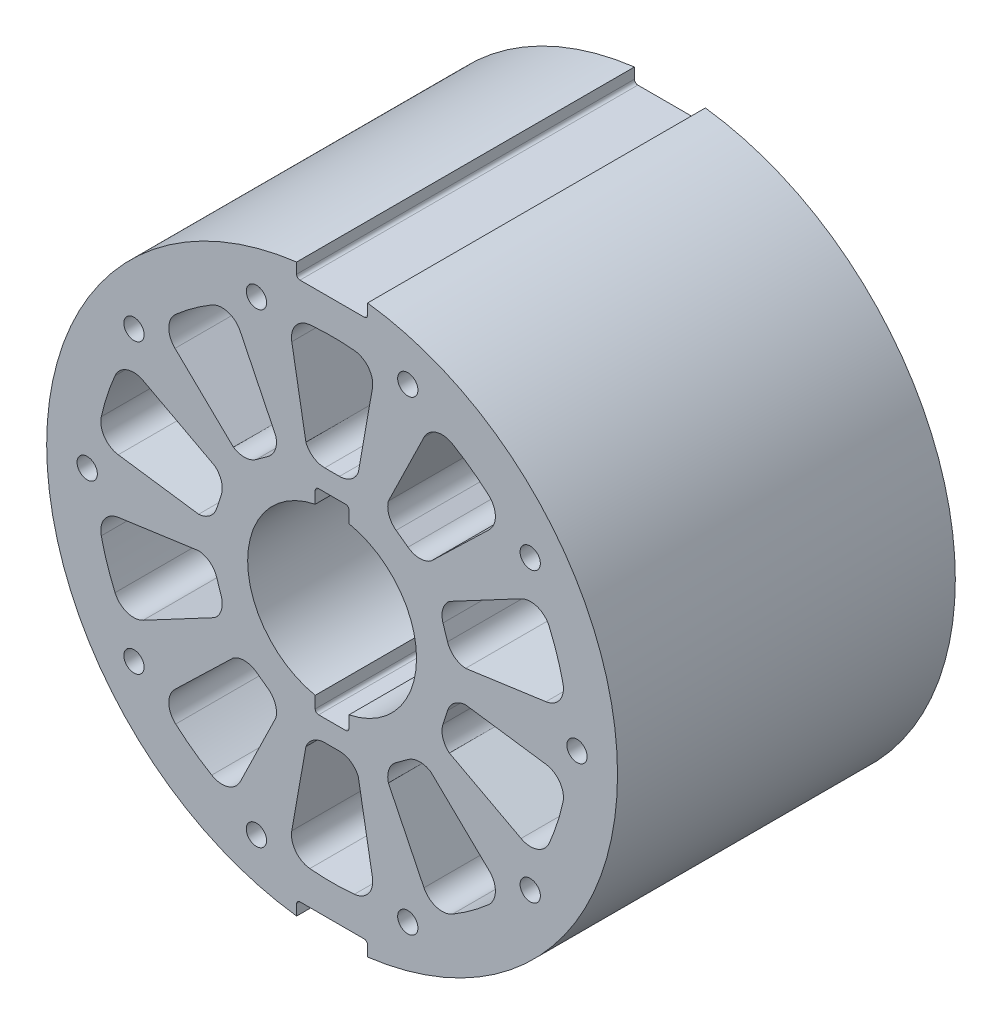
SolidWorks part; units mm, degrees
ref_plane "Ön Düzlem" through (0, 0, 0) normal (0, 0, 1) x (1, 0, 0)
ref_plane "Üst Düzlem" through (0, 0, 0) normal (0, 1, 0) x (1, 0, 0)
ref_plane "Sağ Düzlem" through (0, 0, 0) normal (1, 0, 0) x (0, 0, -1)
sketch "Model" plane through (0, 0, 0) normal (0, 0, 1) x (1, 0, 0)
  line L0 (-9.5, 79.7049) -> (9.5, 79.7049)
  line L1 (60.5945, 121.4987) -> (60.8885, 121.3363)
  line L2 (60.8885, 121.3363) -> (61.139, 121.1124)
  line L3 (61.139, 121.1124) -> (61.3334, 120.8385)
  line L4 (61.3334, 120.8385) -> (61.4619, 120.5282)
  line L5 (61.4619, 120.5282) -> (61.5182, 120.197)
  line L6 (61.5182, 120.197) -> (61.4993, 119.8617)
  line L7 (61.4993, 119.8617) -> (61.4063, 119.5389)
  line L8 (61.4063, 119.5389) -> (45.7726, 92.4605)
  line L9 (45.7726, 92.4605) -> (42.0525, 92.3778)
  line L10 (42.0525, 92.3778) -> (41.4785, 90.992)
  line L11 (58.0621, 81.4174) -> (58.9753, 82.6074)
  line L12 (58.9753, 82.6074) -> (57.1868, 85.8705)
  line L13 (57.1868, 85.8705) -> (72.8206, 112.9489)
  line L14 (72.8206, 112.9489) -> (73.0536, 113.1908)
  line L15 (73.0536, 113.1908) -> (73.3346, 113.3748)
  line L16 (73.3346, 113.3748) -> (73.6495, 113.4917)
  line L17 (73.6495, 113.4917) -> (73.9825, 113.5355)
  line L18 (73.9825, 113.5355) -> (74.317, 113.5041)
  line L19 (74.317, 113.5041) -> (74.636, 113.3991)
  line L20 (74.636, 113.3991) -> (74.9237, 113.2258)
  line L21 (74.9237, 113.2258) -> (89.976, 101.6758)
  line L22 (89.976, 101.6758) -> (90.2179, 101.4427)
  line L23 (90.2179, 101.4427) -> (90.4019, 101.1617)
  line L24 (90.4019, 101.1617) -> (90.5188, 100.8468)
  line L25 (90.5188, 100.8468) -> (90.5626, 100.5138)
  line L26 (90.5626, 100.5138) -> (90.5313, 100.1793)
  line L27 (90.5313, 100.1793) -> (90.4263, 99.8603)
  line L28 (90.4263, 99.8603) -> (90.2529, 99.5726)
  line L29 (90.2529, 99.5726) -> (68.1435, 77.4631)
  line L30 (68.1435, 77.4631) -> (64.5287, 78.3461)
  line L31 (64.5287, 78.3461) -> (63.6156, 77.1561)
  line L32 (77.1561, 63.6156) -> (78.3461, 64.5287)
  line L33 (78.3461, 64.5287) -> (77.4631, 68.1435)
  line L34 (77.4631, 68.1435) -> (99.5726, 90.2529)
  line L35 (99.5726, 90.2529) -> (99.8603, 90.4263)
  line L36 (99.8603, 90.4263) -> (100.1793, 90.5313)
  line L37 (100.1793, 90.5313) -> (100.5138, 90.5626)
  line L38 (100.5138, 90.5626) -> (100.8468, 90.5188)
  line L39 (100.8468, 90.5188) -> (101.1617, 90.4019)
  line L40 (101.1617, 90.4019) -> (101.4427, 90.2179)
  line L41 (101.4427, 90.2179) -> (101.6758, 89.976)
  line L42 (101.6758, 89.976) -> (113.2258, 74.9237)
  line L43 (113.2258, 74.9237) -> (113.3991, 74.636)
  line L44 (113.3991, 74.636) -> (113.5041, 74.317)
  line L45 (113.5041, 74.317) -> (113.5355, 73.9825)
  line L46 (113.5355, 73.9825) -> (113.4917, 73.6495)
  line L47 (113.4917, 73.6495) -> (113.3748, 73.3346)
  line L48 (113.3748, 73.3346) -> (113.1908, 73.0536)
  line L49 (113.1908, 73.0536) -> (112.9489, 72.8206)
  line L50 (112.9489, 72.8206) -> (85.8705, 57.1868)
  line L51 (85.8705, 57.1868) -> (82.6074, 58.9753)
  line L52 (82.6074, 58.9753) -> (81.4174, 58.0621)
  line L53 (90.992, 41.4785) -> (92.3778, 42.0525)
  line L54 (92.3778, 42.0525) -> (92.4605, 45.7726)
  line L55 (92.4605, 45.7726) -> (119.5389, 61.4063)
  line L56 (119.5389, 61.4063) -> (119.8617, 61.4993)
  line L57 (119.8617, 61.4993) -> (120.197, 61.5182)
  line L58 (120.197, 61.5182) -> (120.5282, 61.4619)
  line L59 (120.5282, 61.4619) -> (120.8385, 61.3334)
  line L60 (120.8385, 61.3334) -> (121.1124, 61.139)
  line L61 (121.1124, 61.139) -> (121.3363, 60.8885)
  line L62 (121.3363, 60.8885) -> (121.4987, 60.5945)
  line L63 (121.4987, 60.5945) -> (128.7594, 43.0658)
  line L64 (128.7594, 43.0658) -> (128.8524, 42.743)
  line L65 (128.8524, 42.743) -> (128.8712, 42.4076)
  line L66 (128.8712, 42.4076) -> (128.815, 42.0765)
  line L67 (128.815, 42.0765) -> (128.6864, 41.7662)
  line L68 (128.6864, 41.7662) -> (128.492, 41.4922)
  line L69 (128.492, 41.4922) -> (128.2416, 41.2684)
  line L70 (128.2416, 41.2684) -> (127.9476, 41.1059)
  line L71 (127.9476, 41.1059) -> (97.7455, 33.0133)
  line L72 (97.7455, 33.0133) -> (95.0566, 35.5853)
  line L73 (95.0566, 35.5853) -> (93.6707, 35.0113)
  line L74 (98.6269, 16.5147) -> (100.1141, 16.7105)
  line L75 (100.1141, 16.7105) -> (101.1568, 20.2824)
  line L76 (101.1568, 20.2824) -> (131.3588, 28.375)
  line L77 (131.3588, 28.375) -> (131.6947, 28.3813)
  line L78 (131.6947, 28.3813) -> (132.0235, 28.3127)
  line L79 (132.0235, 28.3127) -> (132.3288, 28.1726)
  line L80 (132.3288, 28.1726) -> (132.5953, 27.9682)
  line L81 (132.5953, 27.9682) -> (132.8096, 27.7095)
  line L82 (132.8096, 27.7095) -> (132.9609, 27.4097)
  line L83 (132.9609, 27.4097) -> (133.0418, 27.0836)
  line L84 (133.0418, 27.0836) -> (135.5183, 8.273)
  line L85 (135.5183, 8.273) -> (135.5246, 7.9371)
  line L86 (135.5246, 7.9371) -> (135.4559, 7.6083)
  line L87 (135.4559, 7.6083) -> (135.3159, 7.303)
  line L88 (135.3159, 7.303) -> (135.1114, 7.0365)
  line L89 (135.1114, 7.0365) -> (134.8528, 6.8222)
  line L90 (134.8528, 6.8222) -> (134.5529, 6.6709)
  line L91 (134.5529, 6.6709) -> (134.2269, 6.59)
  line L92 (134.2269, 6.59) -> (102.9594, 6.59)
  line L93 (102.9594, 6.59) -> (101.0278, 9.7704)
  line L94 (101.0278, 9.7704) -> (99.5406, 9.5746)
  line L95 (99.5406, -9.5746) -> (101.0278, -9.7704)
  line L96 (101.0278, -9.7704) -> (102.9594, -6.59)
  line L97 (102.9594, -6.59) -> (134.2269, -6.59)
  line L98 (134.2269, -6.59) -> (134.5529, -6.6709)
  line L99 (134.5529, -6.6709) -> (134.8528, -6.8222)
  line L100 (134.8528, -6.8222) -> (135.1114, -7.0365)
  line L101 (135.1114, -7.0365) -> (135.3159, -7.303)
  line L102 (135.3159, -7.303) -> (135.4559, -7.6083)
  line L103 (135.4559, -7.6083) -> (135.5246, -7.9371)
  line L104 (135.5246, -7.9371) -> (135.5183, -8.273)
  line L105 (135.5183, -8.273) -> (133.0418, -27.0836)
  line L106 (133.0418, -27.0836) -> (132.9609, -27.4097)
  line L107 (132.9609, -27.4097) -> (132.8096, -27.7095)
  line L108 (132.8096, -27.7095) -> (132.5953, -27.9682)
  line L109 (132.5953, -27.9682) -> (132.3288, -28.1726)
  line L110 (132.3288, -28.1726) -> (132.0235, -28.3127)
  line L111 (132.0235, -28.3127) -> (131.6947, -28.3813)
  line L112 (131.6947, -28.3813) -> (131.3588, -28.375)
  line L113 (131.3588, -28.375) -> (101.1568, -20.2824)
  line L114 (101.1568, -20.2824) -> (100.1141, -16.7105)
  line L115 (100.1141, -16.7105) -> (98.6269, -16.5147)
  line L116 (93.6707, -35.0113) -> (95.0566, -35.5853)
  line L117 (95.0566, -35.5853) -> (97.7455, -33.0133)
  line L118 (97.7455, -33.0133) -> (127.9476, -41.1059)
  line L119 (127.9476, -41.1059) -> (128.2416, -41.2684)
  line L120 (128.2416, -41.2684) -> (128.492, -41.4922)
  line L121 (128.492, -41.4922) -> (128.6864, -41.7662)
  line L122 (128.6864, -41.7662) -> (128.815, -42.0765)
  line L123 (128.815, -42.0765) -> (128.8712, -42.4076)
  line L124 (128.8712, -42.4076) -> (128.8524, -42.743)
  line L125 (128.8524, -42.743) -> (128.7594, -43.0658)
  line L126 (128.7594, -43.0658) -> (121.4987, -60.5945)
  line L127 (121.4987, -60.5945) -> (121.3363, -60.8885)
  line L128 (121.3363, -60.8885) -> (121.1124, -61.139)
  line L129 (121.1124, -61.139) -> (120.8385, -61.3334)
  line L130 (120.8385, -61.3334) -> (120.5282, -61.4619)
  line L131 (120.5282, -61.4619) -> (120.197, -61.5182)
  line L132 (120.197, -61.5182) -> (119.8617, -61.4993)
  line L133 (119.8617, -61.4993) -> (119.5389, -61.4063)
  line L134 (119.5389, -61.4063) -> (92.4605, -45.7726)
  line L135 (92.4605, -45.7726) -> (92.3778, -42.0525)
  line L136 (92.3778, -42.0525) -> (90.992, -41.4785)
  line L137 (81.4174, -58.0621) -> (82.6074, -58.9753)
  line L138 (82.6074, -58.9753) -> (85.8705, -57.1868)
  line L139 (85.8705, -57.1868) -> (112.9489, -72.8206)
  line L140 (112.9489, -72.8206) -> (113.1908, -73.0536)
  line L141 (113.1908, -73.0536) -> (113.3748, -73.3346)
  line L142 (113.3748, -73.3346) -> (113.4917, -73.6495)
  line L143 (113.4917, -73.6495) -> (113.5355, -73.9825)
  line L144 (113.5355, -73.9825) -> (113.5041, -74.317)
  line L145 (113.5041, -74.317) -> (113.3991, -74.636)
  line L146 (113.3991, -74.636) -> (113.2258, -74.9237)
  line L147 (113.2258, -74.9237) -> (101.6758, -89.976)
  line L148 (101.6758, -89.976) -> (101.4427, -90.2179)
  line L149 (101.4427, -90.2179) -> (101.1617, -90.4019)
  line L150 (101.1617, -90.4019) -> (100.8468, -90.5188)
  line L151 (100.8468, -90.5188) -> (100.5138, -90.5626)
  line L152 (100.5138, -90.5626) -> (100.1793, -90.5313)
  line L153 (100.1793, -90.5313) -> (99.8603, -90.4263)
  line L154 (99.8603, -90.4263) -> (99.5726, -90.2529)
  line L155 (99.5726, -90.2529) -> (77.4631, -68.1435)
  line L156 (77.4631, -68.1435) -> (78.3461, -64.5287)
  line L157 (78.3461, -64.5287) -> (77.1561, -63.6156)
  line L158 (63.6156, -77.1561) -> (64.5287, -78.3461)
  line L159 (64.5287, -78.3461) -> (68.1435, -77.4631)
  line L160 (68.1435, -77.4631) -> (90.2529, -99.5726)
  line L161 (90.2529, -99.5726) -> (90.4263, -99.8603)
  line L162 (90.4263, -99.8603) -> (90.5313, -100.1793)
  line L163 (90.5313, -100.1793) -> (90.5626, -100.5138)
  line L164 (90.5626, -100.5138) -> (90.5188, -100.8468)
  line L165 (90.5188, -100.8468) -> (90.4019, -101.1617)
  line L166 (90.4019, -101.1617) -> (90.2179, -101.4427)
  line L167 (90.2179, -101.4427) -> (89.976, -101.6758)
  line L168 (89.976, -101.6758) -> (74.9237, -113.2258)
  line L169 (74.9237, -113.2258) -> (74.636, -113.3991)
  line L170 (74.636, -113.3991) -> (74.317, -113.5041)
  line L171 (74.317, -113.5041) -> (73.9825, -113.5355)
  line L172 (73.9825, -113.5355) -> (73.6495, -113.4917)
  line L173 (73.6495, -113.4917) -> (73.3346, -113.3748)
  line L174 (73.3346, -113.3748) -> (73.0536, -113.1908)
  line L175 (73.0536, -113.1908) -> (72.8206, -112.9489)
  line L176 (72.8206, -112.9489) -> (57.1868, -85.8705)
  line L177 (57.1868, -85.8705) -> (58.9753, -82.6074)
  line L178 (58.9753, -82.6074) -> (58.0621, -81.4174)
  line L179 (41.4785, -90.992) -> (42.0525, -92.3778)
  line L180 (42.0525, -92.3778) -> (45.7726, -92.4605)
  line L181 (45.7726, -92.4605) -> (61.4063, -119.5389)
  line L182 (61.4063, -119.5389) -> (61.4993, -119.8617)
  line L183 (61.4993, -119.8617) -> (61.5182, -120.197)
  line L184 (61.5182, -120.197) -> (61.4619, -120.5282)
  line L185 (61.4619, -120.5282) -> (61.3334, -120.8385)
  line L186 (61.3334, -120.8385) -> (61.139, -121.1124)
  line L187 (61.139, -121.1124) -> (60.8885, -121.3363)
  line L188 (60.8885, -121.3363) -> (60.5945, -121.4987)
  line L189 (60.5945, -121.4987) -> (43.0658, -128.7594)
  line L190 (43.0658, -128.7594) -> (42.743, -128.8524)
  line L191 (42.743, -128.8524) -> (42.4076, -128.8712)
  line L192 (42.4076, -128.8712) -> (42.0765, -128.815)
  line L193 (42.0765, -128.815) -> (41.7662, -128.6864)
  line L194 (41.7662, -128.6864) -> (41.4922, -128.492)
  line L195 (41.4922, -128.492) -> (41.2684, -128.2416)
  line L196 (41.2684, -128.2416) -> (41.1059, -127.9476)
  line L197 (41.1059, -127.9476) -> (33.0133, -97.7455)
  line L198 (33.0133, -97.7455) -> (35.5853, -95.0566)
  line L199 (35.5853, -95.0566) -> (35.0113, -93.6707)
  line L200 (16.5147, -98.6269) -> (16.7105, -100.1141)
  line L201 (16.7105, -100.1141) -> (20.2824, -101.1568)
  line L202 (20.2824, -101.1568) -> (28.375, -131.3588)
  line L203 (28.375, -131.3588) -> (28.3813, -131.6947)
  line L204 (28.3813, -131.6947) -> (28.3127, -132.0235)
  line L205 (28.3127, -132.0235) -> (28.1726, -132.3288)
  line L206 (28.1726, -132.3288) -> (27.9682, -132.5953)
  line L207 (27.9682, -132.5953) -> (27.7095, -132.8096)
  line L208 (27.7095, -132.8096) -> (27.4097, -132.9609)
  line L209 (27.4097, -132.9609) -> (27.0836, -133.0418)
  line L210 (27.0836, -133.0418) -> (8.273, -135.5183)
  line L211 (8.273, -135.5183) -> (7.9371, -135.5246)
  line L212 (7.9371, -135.5246) -> (7.6083, -135.4559)
  line L213 (7.6083, -135.4559) -> (7.303, -135.3159)
  line L214 (7.303, -135.3159) -> (7.0365, -135.1114)
  line L215 (7.0365, -135.1114) -> (6.8222, -134.8528)
  line L216 (6.8222, -134.8528) -> (6.6709, -134.5529)
  line L217 (6.6709, -134.5529) -> (6.59, -134.2269)
  line L218 (6.59, -134.2269) -> (6.59, -102.9594)
  line L219 (6.59, -102.9594) -> (9.7704, -101.0278)
  line L220 (9.7704, -101.0278) -> (9.5746, -99.5406)
  line L221 (-9.5746, -99.5406) -> (-9.7704, -101.0278)
  line L222 (-9.7704, -101.0278) -> (-6.59, -102.9594)
  line L223 (-6.59, -102.9594) -> (-6.59, -134.2269)
  line L224 (-6.59, -134.2269) -> (-6.6709, -134.5529)
  line L225 (-6.6709, -134.5529) -> (-6.8222, -134.8528)
  line L226 (-6.8222, -134.8528) -> (-7.0365, -135.1114)
  line L227 (-7.0365, -135.1114) -> (-7.303, -135.3159)
  line L228 (-7.303, -135.3159) -> (-7.6083, -135.4559)
  line L229 (-7.6083, -135.4559) -> (-7.9371, -135.5246)
  line L230 (-7.9371, -135.5246) -> (-8.273, -135.5183)
  line L231 (-8.273, -135.5183) -> (-27.0836, -133.0418)
  line L232 (-27.0836, -133.0418) -> (-27.4097, -132.9609)
  line L233 (-27.4097, -132.9609) -> (-27.7095, -132.8096)
  line L234 (-27.7095, -132.8096) -> (-27.9682, -132.5953)
  line L235 (-27.9682, -132.5953) -> (-28.1726, -132.3288)
  line L236 (-28.1726, -132.3288) -> (-28.3127, -132.0235)
  line L237 (-28.3127, -132.0235) -> (-28.3813, -131.6947)
  line L238 (-28.3813, -131.6947) -> (-28.375, -131.3588)
  line L239 (-28.375, -131.3588) -> (-20.2824, -101.1568)
  line L240 (-20.2824, -101.1568) -> (-16.7105, -100.1141)
  line L241 (-16.7105, -100.1141) -> (-16.5147, -98.6269)
  line L242 (-35.0113, -93.6707) -> (-35.5853, -95.0566)
  line L243 (-35.5853, -95.0566) -> (-33.0133, -97.7455)
  line L244 (-33.0133, -97.7455) -> (-41.1059, -127.9476)
  line L245 (-41.1059, -127.9476) -> (-41.2684, -128.2416)
  line L246 (-41.2684, -128.2416) -> (-41.4922, -128.492)
  line L247 (-41.4922, -128.492) -> (-41.7662, -128.6864)
  line L248 (-41.7662, -128.6864) -> (-42.0765, -128.815)
  line L249 (-42.0765, -128.815) -> (-42.4076, -128.8712)
  line L250 (-42.4076, -128.8712) -> (-42.743, -128.8524)
  line L251 (-42.743, -128.8524) -> (-43.0658, -128.7594)
  line L252 (-43.0658, -128.7594) -> (-60.5945, -121.4987)
  line L253 (-60.5945, -121.4987) -> (-60.8885, -121.3363)
  line L254 (-60.8885, -121.3363) -> (-61.139, -121.1124)
  line L255 (-61.139, -121.1124) -> (-61.3334, -120.8385)
  line L256 (-61.3334, -120.8385) -> (-61.4619, -120.5282)
  line L257 (-61.4619, -120.5282) -> (-61.5182, -120.197)
  line L258 (-61.5182, -120.197) -> (-61.4993, -119.8617)
  line L259 (-61.4993, -119.8617) -> (-61.4063, -119.5389)
  line L260 (-61.4063, -119.5389) -> (-45.7726, -92.4605)
  line L261 (-45.7726, -92.4605) -> (-42.0525, -92.3778)
  line L262 (-42.0525, -92.3778) -> (-41.4785, -90.992)
  line L263 (-58.0621, -81.4174) -> (-58.9753, -82.6074)
  line L264 (-58.9753, -82.6074) -> (-57.1868, -85.8705)
  line L265 (-57.1868, -85.8705) -> (-72.8206, -112.9489)
  line L266 (-72.8206, -112.9489) -> (-73.0536, -113.1908)
  line L267 (-73.0536, -113.1908) -> (-73.3346, -113.3748)
  line L268 (-73.3346, -113.3748) -> (-73.6495, -113.4917)
  line L269 (-73.6495, -113.4917) -> (-73.9825, -113.5355)
  line L270 (-73.9825, -113.5355) -> (-74.317, -113.5041)
  line L271 (-74.317, -113.5041) -> (-74.636, -113.3991)
  line L272 (-74.636, -113.3991) -> (-74.9237, -113.2258)
  line L273 (-74.9237, -113.2258) -> (-89.976, -101.6758)
  line L274 (-89.976, -101.6758) -> (-90.2179, -101.4427)
  line L275 (-90.2179, -101.4427) -> (-90.4019, -101.1617)
  line L276 (-90.4019, -101.1617) -> (-90.5188, -100.8468)
  line L277 (-90.5188, -100.8468) -> (-90.5626, -100.5138)
  line L278 (-90.5626, -100.5138) -> (-90.5313, -100.1793)
  line L279 (-90.5313, -100.1793) -> (-90.4263, -99.8603)
  line L280 (-90.4263, -99.8603) -> (-90.2529, -99.5726)
  line L281 (-90.2529, -99.5726) -> (-68.1435, -77.4631)
  line L282 (-68.1435, -77.4631) -> (-64.5287, -78.3461)
  line L283 (-64.5287, -78.3461) -> (-63.6156, -77.1561)
  line L284 (-77.1561, -63.6156) -> (-78.3461, -64.5287)
  line L285 (-78.3461, -64.5287) -> (-77.4631, -68.1435)
  line L286 (-77.4631, -68.1435) -> (-99.5726, -90.2529)
  line L287 (-99.5726, -90.2529) -> (-99.8603, -90.4263)
  line L288 (-99.8603, -90.4263) -> (-100.1793, -90.5313)
  line L289 (-100.1793, -90.5313) -> (-100.5138, -90.5626)
  line L290 (-100.5138, -90.5626) -> (-100.8468, -90.5188)
  line L291 (-100.8468, -90.5188) -> (-101.1617, -90.4019)
  line L292 (-101.1617, -90.4019) -> (-101.4427, -90.2179)
  line L293 (-101.4427, -90.2179) -> (-101.6758, -89.976)
  line L294 (-101.6758, -89.976) -> (-113.2258, -74.9237)
  line L295 (-113.2258, -74.9237) -> (-113.3991, -74.636)
  line L296 (-113.3991, -74.636) -> (-113.5041, -74.317)
  line L297 (-113.5041, -74.317) -> (-113.5355, -73.9825)
  line L298 (-113.5355, -73.9825) -> (-113.4917, -73.6495)
  line L299 (-113.4917, -73.6495) -> (-113.3748, -73.3346)
  line L300 (-113.3748, -73.3346) -> (-113.1908, -73.0536)
  line L301 (-113.1908, -73.0536) -> (-112.9489, -72.8206)
  line L302 (-112.9489, -72.8206) -> (-85.8705, -57.1868)
  line L303 (-85.8705, -57.1868) -> (-82.6074, -58.9753)
  line L304 (-82.6074, -58.9753) -> (-81.4174, -58.0621)
  line L305 (-90.992, -41.4785) -> (-92.3778, -42.0525)
  line L306 (-92.3778, -42.0525) -> (-92.4605, -45.7726)
  line L307 (-92.4605, -45.7726) -> (-119.5389, -61.4063)
  line L308 (-119.5389, -61.4063) -> (-119.8617, -61.4993)
  line L309 (-119.8617, -61.4993) -> (-120.197, -61.5182)
  line L310 (-120.197, -61.5182) -> (-120.5282, -61.4619)
  line L311 (-120.5282, -61.4619) -> (-120.8385, -61.3334)
  line L312 (-120.8385, -61.3334) -> (-121.1124, -61.139)
  line L313 (-121.1124, -61.139) -> (-121.3363, -60.8885)
  line L314 (-121.3363, -60.8885) -> (-121.4987, -60.5945)
  line L315 (-121.4987, -60.5945) -> (-128.7594, -43.0658)
  line L316 (-128.7594, -43.0658) -> (-128.8524, -42.743)
  line L317 (-128.8524, -42.743) -> (-128.8712, -42.4076)
  line L318 (-128.8712, -42.4076) -> (-128.815, -42.0765)
  line L319 (-128.815, -42.0765) -> (-128.6864, -41.7662)
  line L320 (-128.6864, -41.7662) -> (-128.492, -41.4922)
  line L321 (-128.492, -41.4922) -> (-128.2416, -41.2684)
  line L322 (-128.2416, -41.2684) -> (-127.9476, -41.1059)
  line L323 (-127.9476, -41.1059) -> (-97.7455, -33.0133)
  line L324 (-97.7455, -33.0133) -> (-95.0566, -35.5853)
  line L325 (-95.0566, -35.5853) -> (-93.6707, -35.0113)
  line L326 (-98.6269, -16.5147) -> (-100.1141, -16.7105)
  line L327 (-100.1141, -16.7105) -> (-101.1568, -20.2824)
  line L328 (-101.1568, -20.2824) -> (-131.3588, -28.375)
  line L329 (-131.3588, -28.375) -> (-131.6947, -28.3813)
  line L330 (-131.6947, -28.3813) -> (-132.0235, -28.3127)
  line L331 (-132.0235, -28.3127) -> (-132.3288, -28.1726)
  line L332 (-132.3288, -28.1726) -> (-132.5953, -27.9682)
  line L333 (-132.5953, -27.9682) -> (-132.8096, -27.7095)
  line L334 (-132.8096, -27.7095) -> (-132.9609, -27.4097)
  line L335 (-132.9609, -27.4097) -> (-133.0418, -27.0836)
  line L336 (-133.0418, -27.0836) -> (-135.5183, -8.273)
  line L337 (-135.5183, -8.273) -> (-135.5246, -7.9371)
  line L338 (-135.5246, -7.9371) -> (-135.4559, -7.6083)
  line L339 (-135.4559, -7.6083) -> (-135.3159, -7.303)
  line L340 (-135.3159, -7.303) -> (-135.1114, -7.0365)
  line L341 (-135.1114, -7.0365) -> (-134.8528, -6.8222)
  line L342 (-134.8528, -6.8222) -> (-134.5529, -6.6709)
  line L343 (-134.5529, -6.6709) -> (-134.2269, -6.59)
  line L344 (-134.2269, -6.59) -> (-102.9594, -6.59)
  line L345 (-102.9594, -6.59) -> (-101.0278, -9.7704)
  line L346 (-101.0278, -9.7704) -> (-99.5406, -9.5746)
  line L347 (-99.5406, 9.5746) -> (-101.0278, 9.7704)
  line L348 (-101.0278, 9.7704) -> (-102.9594, 6.59)
  line L349 (-102.9594, 6.59) -> (-134.2269, 6.59)
  line L350 (-134.2269, 6.59) -> (-134.5529, 6.6709)
  line L351 (-134.5529, 6.6709) -> (-134.8528, 6.8222)
  line L352 (-134.8528, 6.8222) -> (-135.1114, 7.0365)
  line L353 (-135.1114, 7.0365) -> (-135.3159, 7.303)
  line L354 (-135.3159, 7.303) -> (-135.4559, 7.6083)
  line L355 (-135.4559, 7.6083) -> (-135.5246, 7.9371)
  line L356 (-135.5246, 7.9371) -> (-135.5183, 8.273)
  line L357 (-135.5183, 8.273) -> (-133.0418, 27.0836)
  line L358 (-133.0418, 27.0836) -> (-132.9609, 27.4097)
  line L359 (-132.9609, 27.4097) -> (-132.8096, 27.7095)
  line L360 (-132.8096, 27.7095) -> (-132.5953, 27.9682)
  line L361 (-132.5953, 27.9682) -> (-132.3288, 28.1726)
  line L362 (-132.3288, 28.1726) -> (-132.0235, 28.3127)
  line L363 (-132.0235, 28.3127) -> (-131.6947, 28.3813)
  line L364 (-131.6947, 28.3813) -> (-131.3588, 28.375)
  line L365 (-131.3588, 28.375) -> (-101.1568, 20.2824)
  line L366 (-101.1568, 20.2824) -> (-100.1141, 16.7105)
  line L367 (-100.1141, 16.7105) -> (-98.6269, 16.5147)
  line L368 (-93.6707, 35.0113) -> (-95.0566, 35.5853)
  line L369 (-95.0566, 35.5853) -> (-97.7455, 33.0133)
  line L370 (-97.7455, 33.0133) -> (-127.9476, 41.1059)
  line L371 (-127.9476, 41.1059) -> (-128.2416, 41.2684)
  line L372 (-128.2416, 41.2684) -> (-128.492, 41.4922)
  line L373 (-128.492, 41.4922) -> (-128.6864, 41.7662)
  line L374 (-128.6864, 41.7662) -> (-128.815, 42.0765)
  line L375 (-128.815, 42.0765) -> (-128.8712, 42.4076)
  line L376 (-128.8712, 42.4076) -> (-128.8524, 42.743)
  line L377 (-128.8524, 42.743) -> (-128.7594, 43.0658)
  line L378 (-128.7594, 43.0658) -> (-121.4987, 60.5945)
  line L379 (-121.4987, 60.5945) -> (-121.3363, 60.8885)
  line L380 (-121.3363, 60.8885) -> (-121.1124, 61.139)
  line L381 (-121.1124, 61.139) -> (-120.8385, 61.3334)
  line L382 (-120.8385, 61.3334) -> (-120.5282, 61.4619)
  line L383 (-120.5282, 61.4619) -> (-120.197, 61.5182)
  line L384 (-120.197, 61.5182) -> (-119.8617, 61.4993)
  line L385 (-119.8617, 61.4993) -> (-119.5389, 61.4063)
  line L386 (-119.5389, 61.4063) -> (-92.4605, 45.7726)
  line L387 (-92.4605, 45.7726) -> (-92.3778, 42.0525)
  line L388 (-92.3778, 42.0525) -> (-90.992, 41.4785)
  line L389 (-81.4174, 58.0621) -> (-82.6074, 58.9753)
  line L390 (-82.6074, 58.9753) -> (-85.8705, 57.1868)
  line L391 (-85.8705, 57.1868) -> (-112.9489, 72.8206)
  line L392 (-112.9489, 72.8206) -> (-113.1908, 73.0536)
  line L393 (-113.1908, 73.0536) -> (-113.3748, 73.3346)
  line L394 (-113.3748, 73.3346) -> (-113.4917, 73.6495)
  line L395 (-113.4917, 73.6495) -> (-113.5355, 73.9825)
  line L396 (-113.5355, 73.9825) -> (-113.5041, 74.317)
  line L397 (-113.5041, 74.317) -> (-113.3991, 74.636)
  line L398 (-113.3991, 74.636) -> (-113.2258, 74.9237)
  line L399 (-113.2258, 74.9237) -> (-101.6758, 89.976)
  line L400 (-101.6758, 89.976) -> (-101.4427, 90.2179)
  line L401 (-101.4427, 90.2179) -> (-101.1617, 90.4019)
  line L402 (-101.1617, 90.4019) -> (-100.8468, 90.5188)
  line L403 (-100.8468, 90.5188) -> (-100.5138, 90.5626)
  line L404 (-100.5138, 90.5626) -> (-100.1793, 90.5313)
  line L405 (-100.1793, 90.5313) -> (-99.8603, 90.4263)
  line L406 (-99.8603, 90.4263) -> (-99.5726, 90.2529)
  line L407 (-99.5726, 90.2529) -> (-77.4631, 68.1435)
  line L408 (-77.4631, 68.1435) -> (-78.3461, 64.5287)
  line L409 (-78.3461, 64.5287) -> (-77.1561, 63.6156)
  line L410 (-63.6156, 77.1561) -> (-64.5287, 78.3461)
  line L411 (-64.5287, 78.3461) -> (-68.1435, 77.4631)
  line L412 (-68.1435, 77.4631) -> (-90.2529, 99.5726)
  line L413 (-90.2529, 99.5726) -> (-90.4263, 99.8603)
  line L414 (-90.4263, 99.8603) -> (-90.5313, 100.1793)
  line L415 (-90.5313, 100.1793) -> (-90.5626, 100.5138)
  line L416 (-90.5626, 100.5138) -> (-90.5188, 100.8468)
  line L417 (-90.5188, 100.8468) -> (-90.4019, 101.1617)
  line L418 (-90.4019, 101.1617) -> (-90.2179, 101.4427)
  line L419 (-90.2179, 101.4427) -> (-89.976, 101.6758)
  line L420 (-89.976, 101.6758) -> (-74.9237, 113.2258)
  line L421 (-74.9237, 113.2258) -> (-74.636, 113.3991)
  line L422 (-74.636, 113.3991) -> (-74.317, 113.5041)
  line L423 (-74.317, 113.5041) -> (-73.9825, 113.5355)
  line L424 (-73.9825, 113.5355) -> (-73.6495, 113.4917)
  line L425 (-73.6495, 113.4917) -> (-73.3346, 113.3748)
  line L426 (-73.3346, 113.3748) -> (-73.0536, 113.1908)
  line L427 (-73.0536, 113.1908) -> (-72.8206, 112.9489)
  line L428 (-72.8206, 112.9489) -> (-57.1868, 85.8705)
  line L429 (-57.1868, 85.8705) -> (-58.9753, 82.6074)
  line L430 (-58.9753, 82.6074) -> (-58.0621, 81.4174)
  line L431 (-41.4785, 90.992) -> (-42.0525, 92.3778)
  line L432 (-42.0525, 92.3778) -> (-45.7726, 92.4605)
  line L433 (-45.7726, 92.4605) -> (-61.4063, 119.5389)
  line L434 (-61.4063, 119.5389) -> (-61.4993, 119.8617)
  line L435 (-61.4993, 119.8617) -> (-61.5182, 120.197)
  line L436 (-61.5182, 120.197) -> (-61.4619, 120.5282)
  line L437 (-61.4619, 120.5282) -> (-61.3334, 120.8385)
  line L438 (-61.3334, 120.8385) -> (-61.139, 121.1124)
  line L439 (-61.139, 121.1124) -> (-60.8885, 121.3363)
  line L440 (-60.8885, 121.3363) -> (-60.5945, 121.4987)
  line L441 (-60.5945, 121.4987) -> (-43.0658, 128.7594)
  line L442 (-43.0658, 128.7594) -> (-42.743, 128.8524)
  line L443 (-42.743, 128.8524) -> (-42.4076, 128.8712)
  line L444 (-42.4076, 128.8712) -> (-42.0765, 128.815)
  line L445 (-42.0765, 128.815) -> (-41.7662, 128.6864)
  line L446 (-41.7662, 128.6864) -> (-41.4922, 128.492)
  line L447 (-41.4922, 128.492) -> (-41.2684, 128.2416)
  line L448 (-41.2684, 128.2416) -> (-41.1059, 127.9476)
  line L449 (-41.1059, 127.9476) -> (-33.0133, 97.7455)
  line L450 (-33.0133, 97.7455) -> (-35.5853, 95.0566)
  line L451 (-35.5853, 95.0566) -> (-35.0113, 93.6707)
  line L452 (-16.5147, 98.6269) -> (-16.7105, 100.1141)
  line L453 (-16.7105, 100.1141) -> (-20.2824, 101.1568)
  line L454 (-20.2824, 101.1568) -> (-28.375, 131.3588)
  line L455 (-28.375, 131.3588) -> (-28.3813, 131.6947)
  line L456 (-28.3813, 131.6947) -> (-28.3127, 132.0235)
  line L457 (-28.3127, 132.0235) -> (-28.1726, 132.3288)
  line L458 (-28.1726, 132.3288) -> (-27.9682, 132.5953)
  line L459 (-27.9682, 132.5953) -> (-27.7095, 132.8096)
  line L460 (-27.7095, 132.8096) -> (-27.4097, 132.9609)
  line L461 (-27.4097, 132.9609) -> (-27.0836, 133.0418)
  line L462 (-27.0836, 133.0418) -> (-8.273, 135.5183)
  line L463 (-8.273, 135.5183) -> (-7.9371, 135.5246)
  line L464 (-7.9371, 135.5246) -> (-7.6083, 135.4559)
  line L465 (-7.6083, 135.4559) -> (-7.303, 135.3159)
  line L466 (-7.303, 135.3159) -> (-7.0365, 135.1114)
  line L467 (-7.0365, 135.1114) -> (-6.8222, 134.8528)
  line L468 (-6.8222, 134.8528) -> (-6.6709, 134.5529)
  line L469 (-6.6709, 134.5529) -> (-6.59, 134.2269)
  line L470 (-6.59, 134.2269) -> (-6.59, 102.9594)
  line L471 (-6.59, 102.9594) -> (-9.7704, 101.0278)
  line L472 (-9.7704, 101.0278) -> (-9.5746, 99.5406)
  line L473 (9.5746, 99.5406) -> (9.7704, 101.0278)
  line L474 (9.7704, 101.0278) -> (6.59, 102.9594)
  line L475 (6.59, 102.9594) -> (6.59, 134.2269)
  line L476 (6.59, 134.2269) -> (6.6709, 134.5529)
  line L477 (6.6709, 134.5529) -> (6.8222, 134.8528)
  line L478 (6.8222, 134.8528) -> (7.0365, 135.1114)
  line L479 (7.0365, 135.1114) -> (7.303, 135.3159)
  line L480 (7.303, 135.3159) -> (7.6083, 135.4559)
  line L481 (7.6083, 135.4559) -> (7.9371, 135.5246)
  line L482 (7.9371, 135.5246) -> (8.273, 135.5183)
  line L483 (8.273, 135.5183) -> (27.0836, 133.0418)
  line L484 (27.0836, 133.0418) -> (27.4097, 132.9609)
  line L485 (27.4097, 132.9609) -> (27.7095, 132.8096)
  line L486 (27.7095, 132.8096) -> (27.9682, 132.5953)
  line L487 (27.9682, 132.5953) -> (28.1726, 132.3288)
  line L488 (28.1726, 132.3288) -> (28.3127, 132.0235)
  line L489 (28.3127, 132.0235) -> (28.3813, 131.6947)
  line L490 (28.3813, 131.6947) -> (28.375, 131.3588)
  line L491 (28.375, 131.3588) -> (20.2824, 101.1568)
  line L492 (20.2824, 101.1568) -> (16.7105, 100.1141)
  line L493 (16.7105, 100.1141) -> (16.5147, 98.6269)
  line L494 (35.0113, 93.6707) -> (35.5853, 95.0566)
  line L495 (35.5853, 95.0566) -> (33.0133, 97.7455)
  line L496 (33.0133, 97.7455) -> (41.1059, 127.9476)
  line L497 (41.1059, 127.9476) -> (41.2684, 128.2416)
  line L498 (41.2684, 128.2416) -> (41.4922, 128.492)
  line L499 (41.4922, 128.492) -> (41.7662, 128.6864)
  line L500 (41.7662, 128.6864) -> (42.0765, 128.815)
  line L501 (42.0765, 128.815) -> (42.4076, 128.8712)
  line L502 (42.4076, 128.8712) -> (42.743, 128.8524)
  line L503 (42.743, 128.8524) -> (43.0658, 128.7594)
  line L504 (43.0658, 128.7594) -> (60.5945, 121.4987)
  line L505 (-9.5, 80.2049) -> (9.5, 80.2049)
  line L506 (10.5, 80.7049) -> (10.5, 83.8451)
  line L507 (10.5, -80.7049) -> (10.5, -83.8451)
  line L508 (27.7776, -94.5021) -> (26.5086, -90.1848)
  line L509 (2.6574, -93.9624) -> (2.7847, -98.4606)
  line L510 (-27.7776, 94.5021) -> (-26.5086, 90.1848)
  line L511 (-2.6574, 93.9624) -> (-2.7847, 98.4606)
  line L512 (94.5021, 27.7776) -> (90.1848, 26.5086)
  line L513 (93.9624, 2.6574) -> (98.4606, 2.7847)
  line L514 (-94.5021, -27.7776) -> (-90.1848, -26.5086)
  line L515 (-93.9624, -2.6574) -> (-98.4606, -2.7847)
  line L516 (55.6209, -81.2931) -> (53.0798, -77.5792)
  line L517 (31.5634, -88.5424) -> (33.0744, -92.7811)
  line L518 (-55.6209, 81.2931) -> (-53.0798, 77.5792)
  line L519 (-31.5634, 88.5424) -> (-33.0744, 92.7811)
  line L520 (81.2931, 55.6209) -> (77.5792, 53.0798)
  line L521 (88.5424, 31.5634) -> (92.7811, 33.0744)
  line L522 (-81.2931, -55.6209) -> (-77.5792, -53.0798)
  line L523 (-88.5424, -31.5634) -> (-92.7811, -33.0744)
  line L524 (78.0195, -60.1265) -> (74.4552, -57.3796)
  line L525 (57.3796, -74.4552) -> (60.1265, -78.0195)
  line L526 (-78.0195, 60.1265) -> (-74.4552, 57.3796)
  line L527 (-57.3796, 74.4552) -> (-60.1265, 78.0195)
  line L528 (60.1265, 78.0195) -> (57.3796, 74.4552)
  line L529 (74.4552, 57.3796) -> (78.0195, 60.1265)
  line L530 (-60.1265, -78.0195) -> (-57.3796, -74.4552)
  line L531 (-74.4552, -57.3796) -> (-78.0195, -60.1265)
  line L532 (92.7811, -33.0744) -> (88.5424, -31.5634)
  line L533 (77.5792, -53.0798) -> (81.2931, -55.6209)
  line L534 (-92.7811, 33.0744) -> (-88.5424, 31.5634)
  line L535 (-77.5792, 53.0798) -> (-81.2931, 55.6209)
  line L536 (33.0744, 92.7811) -> (31.5634, 88.5424)
  line L537 (53.0798, 77.5792) -> (55.6209, 81.2931)
  line L538 (-33.0744, -92.7811) -> (-31.5634, -88.5424)
  line L539 (-53.0798, -77.5792) -> (-55.6209, -81.2931)
  line L540 (98.4606, -2.7847) -> (93.9624, -2.6574)
  line L541 (90.1848, -26.5086) -> (94.5021, -27.7776)
  line L542 (-98.4606, 2.7847) -> (-93.9624, 2.6574)
  line L543 (-90.1848, 26.5086) -> (-94.5021, 27.7776)
  line L544 (2.7847, 98.4606) -> (2.6574, 93.9624)
  line L545 (26.5086, 90.1848) -> (27.7776, 94.5021)
  line L546 (-2.7847, -98.4606) -> (-2.6574, -93.9624)
  line L547 (-26.5086, -90.1848) -> (-27.7776, -94.5021)
  line L548 (9.5, -79.7049) -> (-9.5, -79.7049)
  line L549 (10, 80.7049) -> (10, 84.4097)
  line L550 (-10.5, -80.7049) -> (-10.5, -83.8451)
  line L551 (-10, 80.7049) -> (-10, 84.4097)
  line L552 (9.5, -80.2049) -> (-9.5, -80.2049)
  line L553 (-10, -80.7049) -> (-10, -84.4097)
  line L554 (10, -80.7049) -> (10, -84.4097)
  line L555 (-10.5, 80.7049) -> (-10.5, 83.8451)
  line L556 (-7.7629, 39.0257) -> (-11.9363, 62.6943)
  line L557 (7.7629, 39.0257) -> (11.9363, 62.6943)
  line L558 (16.6584, 36.1354) -> (27.1941, 57.7368)
  line L559 (29.2191, 27.0095) -> (46.5075, 43.7048)
  line L560 (22.4686, 27.2158) -> (18.9406, 29.779)
  line L561 (34.7168, 19.4426) -> (55.9373, 30.7257)
  line L562 (39.5145, 4.6766) -> (63.3144, 8.0215)
  line L563 (34.1745, 8.8113) -> (32.8269, 12.9587)
  line L564 (39.5145, -4.6766) -> (63.3144, -8.0215)
  line L565 (34.7168, -19.4426) -> (55.9373, -30.7257)
  line L566 (32.8269, -12.9587) -> (34.1745, -8.8113)
  line L567 (29.2191, -27.0095) -> (46.5075, -43.7048)
  line L568 (16.6584, -36.1354) -> (27.1941, -57.7368)
  line L569 (18.9406, -29.779) -> (22.4686, -27.2158)
  line L570 (7.7629, -39.0257) -> (11.9363, -62.6943)
  line L571 (-7.7629, -39.0257) -> (-11.9363, -62.6943)
  line L572 (-2.1804, -35.2247) -> (2.1804, -35.2247)
  line L573 (-16.6584, -36.1354) -> (-27.1941, -57.7368)
  line L574 (-29.2191, -27.0095) -> (-46.5075, -43.7048)
  line L575 (-22.4686, -27.2158) -> (-18.9406, -29.779)
  line L576 (-5, -24.4949) -> (-5, -27.9898)
  line L577 (5, 24.4949) -> (5, 27.9898)
  line L578 (-34.7168, -19.4426) -> (-55.9373, -30.7257)
  line L579 (-39.5145, -4.6766) -> (-63.3144, -8.0215)
  line L580 (2.1804, 35.2247) -> (-2.1804, 35.2247)
  line L581 (-34.1745, -8.8113) -> (-32.8269, -12.9587)
  line L582 (-39.5145, 4.6766) -> (-63.3144, 8.0215)
  line L583 (-34.7168, 19.4426) -> (-55.9373, 30.7257)
  line L584 (-32.8269, 12.9587) -> (-34.1745, 8.8113)
  line L585 (-29.2191, 27.0095) -> (-46.5075, 43.7048)
  line L586 (-16.6584, 36.1354) -> (-27.1941, 57.7368)
  line L587 (-18.9406, 29.779) -> (-22.4686, 27.2158)
  line L588 (-5, 24.4949) -> (-5, 27.9898)
  line L589 (0, 28.9898) -> (-4, 28.9898)
  line L590 (5, -24.4949) -> (5, -27.9898)
  line L591 (0, -28.9898) -> (4, -28.9898)
  line L592 (0, 28.9898) -> (4, 28.9898)
  line L593 (0, -28.9898) -> (-4, -28.9898)
  arc A0 (145, 0) -> (64.7137, 129.758) centre (0, 0) ccw
  arc A1 (58.0621, 81.4174) -> (41.4785, 90.992) centre (0, 0) ccw
  arc A2 (77.1561, 63.6156) -> (63.6156, 77.1561) centre (0, 0) ccw
  arc A3 (90.992, 41.4785) -> (81.4174, 58.0621) centre (0, 0) ccw
  arc A4 (98.6269, 16.5147) -> (93.6707, 35.0113) centre (0, 0) ccw
  arc A5 (99.5406, -9.5746) -> (99.5406, 9.5746) centre (0, 0) ccw
  arc A6 (93.6707, -35.0113) -> (98.6269, -16.5147) centre (0, 0) ccw
  arc A7 (81.4174, -58.0621) -> (90.992, -41.4785) centre (0, 0) ccw
  arc A8 (63.6156, -77.1561) -> (77.1561, -63.6156) centre (0, 0) ccw
  arc A9 (41.4785, -90.992) -> (58.0621, -81.4174) centre (0, 0) ccw
  arc A10 (16.5147, -98.6269) -> (35.0113, -93.6707) centre (0, 0) ccw
  arc A11 (-9.5746, -99.5406) -> (9.5746, -99.5406) centre (0, 0) ccw
  arc A12 (-35.0113, -93.6707) -> (-16.5147, -98.6269) centre (0, 0) ccw
  arc A13 (-58.0621, -81.4174) -> (-41.4785, -90.992) centre (0, 0) ccw
  arc A14 (-77.1561, -63.6156) -> (-63.6156, -77.1561) centre (0, 0) ccw
  arc A15 (-90.992, -41.4785) -> (-81.4174, -58.0621) centre (0, 0) ccw
  arc A16 (-98.6269, -16.5147) -> (-93.6707, -35.0113) centre (0, 0) ccw
  arc A17 (-99.5406, 9.5746) -> (-99.5406, -9.5746) centre (0, 0) ccw
  arc A18 (-93.6707, 35.0113) -> (-98.6269, 16.5147) centre (0, 0) ccw
  arc A19 (-81.4174, 58.0621) -> (-90.992, 41.4785) centre (0, 0) ccw
  arc A20 (-63.6156, 77.1561) -> (-77.1561, 63.6156) centre (0, 0) ccw
  arc A21 (-41.4785, 90.992) -> (-58.0621, 81.4174) centre (0, 0) ccw
  arc A22 (-16.5147, 98.6269) -> (-35.0113, 93.6707) centre (0, 0) ccw
  arc A23 (9.5746, 99.5406) -> (-9.5746, 99.5406) centre (0, 0) ccw
  arc A24 (35.0113, 93.6707) -> (16.5147, 98.6269) centre (0, 0) ccw
  arc A25 (64.7137, 129.758) -> (145, 0) centre (0, 0) ccw
  arc A26 (94, 0) -> (-94, 0) centre (0, 0) ccw
  arc A27 (-10, 84.4097) -> (-10, -84.4097) centre (0, 0) ccw
  arc A28 (-94, 0) -> (94, 0) centre (0, 0) ccw
  arc A29 (2.7847, -98.4606) -> (27.7776, -94.5021) centre (0, 0) ccw
  arc A30 (2.6574, -93.9624) -> (26.5086, -90.1848) centre (0, 0) ccw
  arc A31 (-2.7847, 98.4606) -> (-27.7776, 94.5021) centre (0, 0) ccw
  arc A32 (-2.6574, 93.9624) -> (-26.5086, 90.1848) centre (0, 0) ccw
  arc A33 (98.4606, 2.7847) -> (94.5021, 27.7776) centre (0, 0) ccw
  arc A34 (93.9624, 2.6574) -> (90.1848, 26.5086) centre (0, 0) ccw
  arc A35 (-98.4606, -2.7847) -> (-94.5021, -27.7776) centre (0, 0) ccw
  arc A36 (-93.9624, -2.6574) -> (-90.1848, -26.5086) centre (0, 0) ccw
  arc A37 (33.0744, -92.7811) -> (55.6209, -81.2931) centre (0, 0) ccw
  arc A38 (31.5634, -88.5424) -> (53.0798, -77.5792) centre (0, 0) ccw
  arc A39 (-33.0744, 92.7811) -> (-55.6209, 81.2931) centre (0, 0) ccw
  arc A40 (-31.5634, 88.5424) -> (-53.0798, 77.5792) centre (0, 0) ccw
  arc A41 (92.7811, 33.0744) -> (81.2931, 55.6209) centre (0, 0) ccw
  arc A42 (88.5424, 31.5634) -> (77.5792, 53.0798) centre (0, 0) ccw
  arc A43 (-92.7811, -33.0744) -> (-81.2931, -55.6209) centre (0, 0) ccw
  arc A44 (-88.5424, -31.5634) -> (-77.5792, -53.0798) centre (0, 0) ccw
  arc A45 (60.1265, -78.0195) -> (78.0195, -60.1265) centre (0, 0) ccw
  arc A46 (57.3796, -74.4552) -> (74.4552, -57.3796) centre (0, 0) ccw
  arc A47 (-60.1265, 78.0195) -> (-78.0195, 60.1265) centre (0, 0) ccw
  arc A48 (-57.3796, 74.4552) -> (-74.4552, 57.3796) centre (0, 0) ccw
  arc A49 (78.0195, 60.1265) -> (60.1265, 78.0195) centre (0, 0) ccw
  arc A50 (74.4552, 57.3796) -> (57.3796, 74.4552) centre (0, 0) ccw
  arc A51 (-78.0195, -60.1265) -> (-60.1265, -78.0195) centre (0, 0) ccw
  arc A52 (-74.4552, -57.3796) -> (-57.3796, -74.4552) centre (0, 0) ccw
  arc A53 (81.2931, -55.6209) -> (92.7811, -33.0744) centre (0, 0) ccw
  arc A54 (77.5792, -53.0798) -> (88.5424, -31.5634) centre (0, 0) ccw
  arc A55 (-81.2931, 55.6209) -> (-92.7811, 33.0744) centre (0, 0) ccw
  arc A56 (-77.5792, 53.0798) -> (-88.5424, 31.5634) centre (0, 0) ccw
  arc A57 (55.6209, 81.2931) -> (33.0744, 92.7811) centre (0, 0) ccw
  arc A58 (53.0798, 77.5792) -> (31.5634, 88.5424) centre (0, 0) ccw
  arc A59 (-55.6209, -81.2931) -> (-33.0744, -92.7811) centre (0, 0) ccw
  arc A60 (-53.0798, -77.5792) -> (-31.5634, -88.5424) centre (0, 0) ccw
  arc A61 (94.5021, -27.7776) -> (98.4606, -2.7847) centre (0, 0) ccw
  arc A62 (90.1848, -26.5086) -> (93.9624, -2.6574) centre (0, 0) ccw
  arc A63 (-94.5021, 27.7776) -> (-98.4606, 2.7847) centre (0, 0) ccw
  arc A64 (-90.1848, 26.5086) -> (-93.9624, 2.6574) centre (0, 0) ccw
  arc A65 (27.7776, 94.5021) -> (2.7847, 98.4606) centre (0, 0) ccw
  arc A66 (26.5086, 90.1848) -> (2.6574, 93.9624) centre (0, 0) ccw
  arc A67 (-27.7776, -94.5021) -> (-2.7847, -98.4606) centre (0, 0) ccw
  arc A68 (-26.5086, -90.1848) -> (-2.6574, -93.9624) centre (0, 0) ccw
  arc A69 (9.5, 80.2049) -> (10, 80.7049) centre (9.5, 80.7049) ccw
  arc A70 (-10, 80.7049) -> (-9.5, 80.2049) centre (-9.5, 80.7049) ccw
  arc A71 (-9.5, -80.2049) -> (-10, -80.7049) centre (-9.5, -80.7049) ccw
  arc A72 (10, -80.7049) -> (9.5, -80.2049) centre (9.5, -80.7049) ccw
  arc A73 (10, -84.4097) -> (10, 84.4097) centre (0, 0) ccw
  arc A74 (9.5, 79.7049) -> (10.5, 80.7049) centre (9.5, 80.7049) ccw
  arc A75 (10.5, -83.8451) -> (10.5, 83.8451) centre (0, 0) ccw
  arc A76 (10.5, -80.7049) -> (9.5, -79.7049) centre (9.5, -80.7049) ccw
  arc A77 (-9.5, -79.7049) -> (-10.5, -80.7049) centre (-9.5, -80.7049) ccw
  arc A78 (-10.5, 83.8451) -> (-10.5, -83.8451) centre (0, 0) ccw
  arc A79 (-10.5, 80.7049) -> (-9.5, 79.7049) centre (-9.5, 80.7049) ccw
  arc A80 (6.5924, 69.7096) -> (-6.5924, 69.7096) centre (0, 0) ccw
  arc A81 (-5, 24.4949) -> (-5, -24.4949) centre (0, 0) ccw
  arc A82 (2.1804, 35.2247) -> (7.7629, 39.0257) centre (2.1804, 41.2247) ccw
  arc A83 (46.3076, 52.5213) -> (35.6409, 60.2711) centre (0, 0) ccw
  arc A84 (22.4686, 27.2158) -> (29.2191, 27.0095) centre (25.9953, 32.0699) ccw
  arc A85 (46.3076, 52.5213) -> (46.5075, 43.7048) centre (42.3396, 48.0208) cw
  arc A86 (27.1941, 57.7368) -> (35.6409, 60.2711) centre (32.5869, 55.1066) cw
  arc A87 (18.9406, 29.779) -> (16.6584, 36.1354) centre (22.4673, 34.6331) cw
  arc A88 (68.3349, 15.2717) -> (64.2606, 27.8112) centre (0, 0) ccw
  arc A89 (34.1745, 8.8113) -> (39.5145, 4.6766) centre (39.8808, 10.6654) ccw
  arc A90 (68.3349, 15.2717) -> (63.3144, 8.0215) centre (62.4794, 13.9631) cw
  arc A91 (55.9373, 30.7257) -> (64.2606, 27.8112) centre (58.7542, 25.4281) cw
  arc A92 (32.8269, 12.9587) -> (34.7168, 19.4426) centre (38.5332, 14.8128) cw
  arc A93 (64.2606, -27.8112) -> (68.3349, -15.2717) centre (0, 0) ccw
  arc A94 (32.8269, -12.9587) -> (34.7168, -19.4426) centre (38.5332, -14.8128) ccw
  arc A95 (64.2606, -27.8112) -> (55.9373, -30.7257) centre (58.7542, -25.4281) cw
  arc A96 (63.3144, -8.0215) -> (68.3349, -15.2717) centre (62.4794, -13.9631) cw
  arc A97 (34.1745, -8.8113) -> (39.5145, -4.6766) centre (39.8808, -10.6654) cw
  arc A98 (6.5924, 69.7096) -> (11.9363, 62.6943) centre (6.0275, 63.7362) cw
  arc A99 (35.6409, -60.2711) -> (46.3076, -52.5213) centre (0, 0) ccw
  arc A100 (18.9406, -29.779) -> (16.6584, -36.1354) centre (22.4673, -34.6331) ccw
  arc A101 (-11.9363, 62.6943) -> (-6.5924, 69.7096) centre (-6.0275, 63.7362) cw
  arc A102 (35.6409, -60.2711) -> (27.1941, -57.7368) centre (32.5869, -55.1066) cw
  arc A103 (46.5075, -43.7048) -> (46.3076, -52.5213) centre (42.3396, -48.0208) cw
  arc A104 (22.4686, -27.2158) -> (29.2191, -27.0095) centre (25.9953, -32.0699) cw
  arc A105 (-6.5924, -69.7096) -> (6.5924, -69.7096) centre (0, 0) ccw
  arc A106 (-2.1804, -35.2247) -> (-7.7629, -39.0257) centre (-2.1804, -41.2247) ccw
  arc A107 (-6.5924, -69.7096) -> (-11.9363, -62.6943) centre (-6.0275, -63.7362) cw
  arc A108 (11.9363, -62.6943) -> (6.5924, -69.7096) centre (6.0275, -63.7362) cw
  arc A109 (2.1804, -35.2247) -> (7.7629, -39.0257) centre (2.1804, -41.2247) cw
  arc A110 (-46.3076, -52.5213) -> (-35.6409, -60.2711) centre (0, 0) ccw
  arc A111 (-22.4686, -27.2158) -> (-29.2191, -27.0095) centre (-25.9953, -32.0699) ccw
  arc A112 (-46.3076, -52.5213) -> (-46.5075, -43.7048) centre (-42.3396, -48.0208) cw
  arc A113 (-27.1941, -57.7368) -> (-35.6409, -60.2711) centre (-32.5869, -55.1066) cw
  arc A114 (-18.9406, -29.779) -> (-16.6584, -36.1354) centre (-22.4673, -34.6331) cw
  arc A115 (-68.3349, -15.2717) -> (-64.2606, -27.8112) centre (0, 0) ccw
  arc A116 (-34.1745, -8.8113) -> (-39.5145, -4.6766) centre (-39.8808, -10.6654) ccw
  arc A117 (-68.3349, -15.2717) -> (-63.3144, -8.0215) centre (-62.4794, -13.9631) cw
  arc A118 (-55.9373, -30.7257) -> (-64.2606, -27.8112) centre (-58.7542, -25.4281) cw
  arc A119 (-32.8269, -12.9587) -> (-34.7168, -19.4426) centre (-38.5332, -14.8128) cw
  arc A120 (-64.2606, 27.8112) -> (-68.3349, 15.2717) centre (0, 0) ccw
  arc A121 (-32.8269, 12.9587) -> (-34.7168, 19.4426) centre (-38.5332, 14.8128) ccw
  arc A122 (-64.2606, 27.8112) -> (-55.9373, 30.7257) centre (-58.7542, 25.4281) cw
  arc A123 (-63.3144, 8.0215) -> (-68.3349, 15.2717) centre (-62.4794, 13.9631) cw
  arc A124 (-34.1745, 8.8113) -> (-39.5145, 4.6766) centre (-39.8808, 10.6654) cw
  arc A125 (-35.6409, 60.2711) -> (-46.3076, 52.5213) centre (0, 0) ccw
  arc A126 (-18.9406, 29.779) -> (-16.6584, 36.1354) centre (-22.4673, 34.6331) ccw
  arc A127 (-35.6409, 60.2711) -> (-27.1941, 57.7368) centre (-32.5869, 55.1066) cw
  arc A128 (-46.5075, 43.7048) -> (-46.3076, 52.5213) centre (-42.3396, 48.0208) cw
  arc A129 (-22.4686, 27.2158) -> (-29.2191, 27.0095) centre (-25.9953, 32.0699) cw
  circle A130 centre (-72.5, 0) radius 3
  circle A131 centre (-58.6537, 42.6144) radius 3
  circle A132 centre (-22.4037, 68.9516) radius 3
  circle A133 centre (22.4037, 68.9516) radius 3
  circle A134 centre (58.6537, 42.6144) radius 3
  circle A135 centre (72.5, 0) radius 3
  circle A136 centre (58.6537, -42.6144) radius 3
  circle A137 centre (22.4037, -68.9516) radius 3
  circle A138 centre (-22.4037, -68.9516) radius 3
  circle A139 centre (-58.6537, -42.6144) radius 3
  arc A140 (5, -27.9898) -> (4, -28.9898) centre (4, -27.9898) cw
  arc A141 (-4, -28.9898) -> (-5, -27.9898) centre (-4, -27.9898) cw
  arc A142 (-2.1804, 35.2247) -> (-7.7629, 39.0257) centre (-2.1804, 41.2247) cw
  arc A143 (-5, 27.9898) -> (-4, 28.9898) centre (-4, 27.9898) cw
  arc A144 (4, 28.9898) -> (5, 27.9898) centre (4, 27.9898) cw
  arc A145 (5, -24.4949) -> (5, 24.4949) centre (0, 0) ccw
  point P656 (9.8496, 50.86)
  point P657 (0, 70.0206)
  point P659 (7.0927, 35.2247)
  point P669 (26.4427, 24.3284)
  point P674 (14.9665, 32.6664)
  point P683 (35.6925, 4.1395)
  point P691 (31.3089, 17.6306)
  point P700 (31.3089, -17.6306)
  point P705 (35.6925, -4.1395)
  point P714 (14.9665, -32.6664)
  point P719 (26.4427, -24.3284)
  point P728 (-7.0927, -35.2247)
  point P733 (7.0927, -35.2247)
  point P742 (-26.4427, -24.3284)
  point P747 (-14.9665, -32.6664)
  point P756 (-35.6925, -4.1395)
  point P761 (-31.3089, -17.6306)
  point P770 (-31.3089, 17.6306)
  point P777 (-7.0927, 35.2247)
  point P779 (-35.6925, 4.1395)
  point P790 (-14.9665, 32.6664)
  point P795 (-26.4427, 24.3284)
  point P812 (0, 0)
  point P831 (0, 0)
  dimension "D3" = 2
  dimension "D2" = 10
  dimension "D4" = 6
  dimension "D1" = 0.5
extrude "Yükseklik-Ekstrüzyon5" add sketch "Model" along normal blind 100 contours A79 L555 A78 L550 A77 L548 A76 L507 A75 L506 A74 L0 A145 L590 A140 L591 L593 A141 L576 A81 L588 A143 L589 L592 A144 L577 A139 A138 A137 A136 A135 A134 A133 A132 A131 A130 L560 A87 L558 region at (0, 77.3241, 0)
